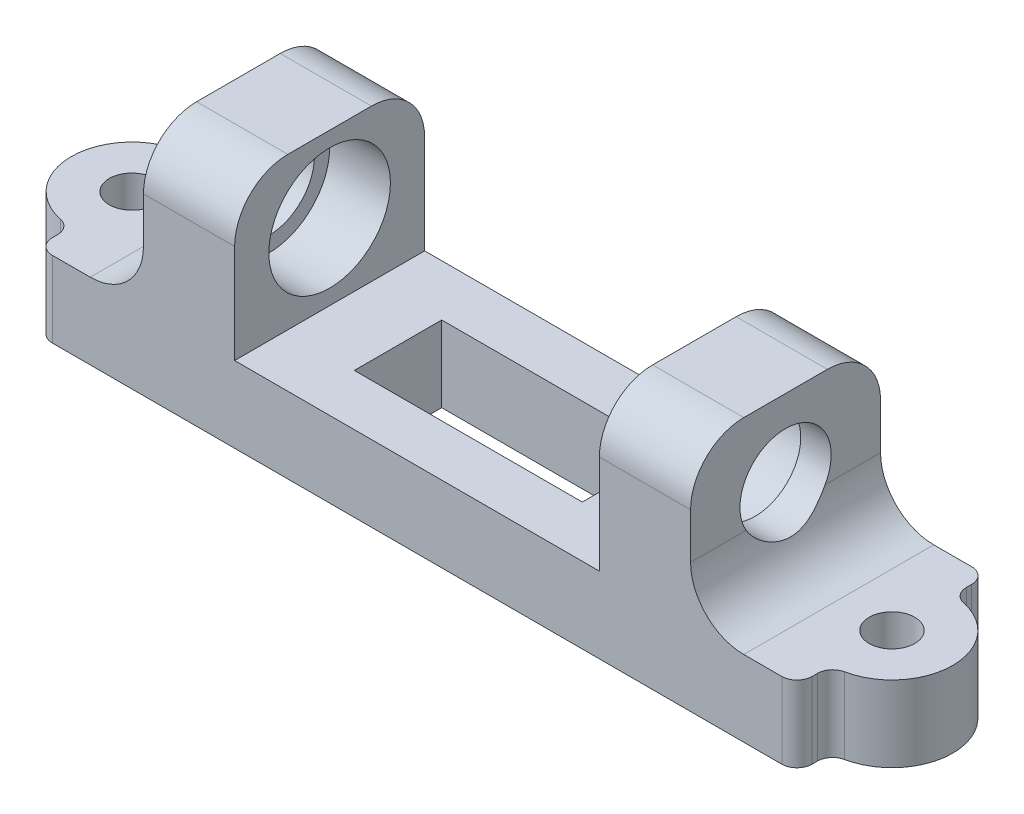
SolidWorks part; units mm, degrees
ref_plane "Front Plane" through (0, 0, 0) normal (0, 0, 1) x (1, 0, 0)
ref_plane "Top Plane" through (0, 0, 0) normal (0, 1, 0) x (1, 0, 0)
ref_plane "Right Plane" through (0, 0, 0) normal (1, 0, 0) x (0, 0, -1)
sketch "Sketch1" plane through (0, 0, 0) normal (0, 1, 0) x (1, 0, 0)
  line L0 (-25, -6.25) -> (-25, 6.25)
  line L1 (-25, -6.25) -> (25, -6.25)
  line L2 (-25, 6.25) -> (25, 6.25)
  line L3 (25, -6.25) -> (25, 6.25)
  line L4 (-25, -6.25) -> (25, 6.25) construction
  line L5 (-25, 6.25) -> (25, -6.25) construction
  circle A0 centre (-25, 0) radius 1.5
  circle A1 centre (25, 0) radius 1.5
  circle A2 centre (-25, 0) radius 4
  circle A3 centre (25, 0) radius 4
  point P1 (0, 0)
  dimension "D3" = 3
  dimension "D4" = 3
  dimension "D5" = 8
  dimension "D6" = 8
  dimension "D1" = 50
  dimension "D2" = 12.5
extrude "Boss-Extrude1" add sketch "Sketch1" along normal blind 5 contours A3 L3 L2 L0 A2 L1 | L0 A2 A0 | L0 A2 A0 | L3 A3 A1 | L3 A3 A1 region at (0, 0, 0) region at (-26.8713, 0, 0) region at (-23.1287, 0, 0) region at (23.1287, 0, 0) region at (26.8713, 0, 0)
sketch "Sketch2" plane through (0, 5, 0) normal (0, 1, 0) x (1, 0, 0)
  line L0 (-25, 1.5) -> (-25, -1.5)
  line L1 (-25, 0) -> (-15, 0)
  line L2 (-18, -6.25) -> (-18, 6.25)
  line L3 (-18, -6.25) -> (-12, -6.25)
  line L4 (-18, 6.25) -> (-12, 6.25)
  line L5 (-12, -6.25) -> (-12, 6.25)
  line L6 (-18, -6.25) -> (-12, 6.25) construction
  line L7 (-18, 6.25) -> (-12, -6.25) construction
  circle A0 centre (-25, 0) radius 1.5 construction
  dimension "D1" = 10
  dimension "D2" = 6
  dimension "D3" = 12.5
extrude "Boss-Extrude2" add sketch "Sketch2" along normal blind 10 contours L3 L5 L4 L2 region at (-17.8613, 5, 3.125)
sketch "Sketch3" plane through (-12, 0, 0) normal (1, 0, 0) x (0, 0, -1)
  line L0 (0, 15) -> (0, 5)
  line L1 (-6.25, 15) -> (6.25, 15) construction
  line L2 (-6.25, 5) -> (6.25, 5) construction
  circle A0 centre (0, 10) radius 4
  circle A1 centre (0, 10) radius 3
  dimension "D1" = 8
  dimension "D2" = 6
extrude "Cut-Extrude1" cut sketch "Sketch3" against normal blind 4 contours A0
extrude "Cut-Extrude2" cut sketch "Sketch3<3>" against normal through all contours A1
sketch "Sketch3<3>" plane through (-12, 0, 0) normal (1, 0, 0) x (0, 0, -1) same geometry as "Sketch3"
fillet "Fillet6" radius 3.5 1 edges at (-18, 5, 0) type face fillet first side face at (-18, 10, 3) second side face at (-25, 5, 1.5)
fillet "Fillet7" radius 3.5 1 edges at (-15, 15, -6.25) type face fillet first side face at (-8.975, 6.4195, -6.25) second side face at (-15, 15, 0)
fillet "Fillet8" radius 3.5 1 edges at (-15, 15, 6.25) type face fillet first side face at (-8.975, 6.4195, 6.25) second side face at (-15, 15, 1.75)
mirror "Mirror4" about plane through (0, 0, 0) normal (1, 0, 0) of "Cut-Extrude2", "Cut-Extrude1", "Boss-Extrude2"
fillet "Fillet9" radius 3.5 1 edges at (15, 15, -6.25) type face fillet first side face at (15, 15, 0) second side face at (-1.5981, 6.9827, -6.25)
fillet "Fillet10" radius 3.5 1 edges at (15, 15, 6.25) type face fillet first side face at (-1.5981, 6.9827, 6.25) second side face at (15, 15, 1.75)
fillet "Fillet11" radius 3.5 1 edges at (18, 5, 0) type face fillet first side face at (18, 10, 3) second side face at (25, 5, 1.5)
fillet "Fillet12" radius 1 1 edges at (25, 2.5, -6.25) type face fillet first side face at (25, 2.5, -5.125) second side face at (0, 6.5393, -6.25)
fillet "Fillet13" radius 1 1 edges at (25, 2.5, 6.25) type face fillet first side face at (25, 2.5, 5.125) second side face at (0, 6.5393, 6.25)
fillet "Fillet14" radius 1 1 edges at (-25, 2.5, 6.25) type face fillet first side face at (-0.1429, 6.5393, 6.25) second side face at (-25, 2.5, 5.125)
fillet "Fillet15" radius 1 1 edges at (-25, 2.5, -6.25) type face fillet first side face at (-25, 2.5, -5.125) second side face at (-0.1429, 6.5393, -6.25)
fillet "Fillet16" radius 1 1 edges at (-25, 2.5, -4) type face fillet first side face at (-25, 2.5, -4.625) second side face at (-27, 2.5, 0)
fillet "Fillet17" radius 1 1 edges at (-25, 2.5, 4) type face fillet first side face at (-27.1899, 2.5, 0.2212) second side face at (-25, 2.5, 4.625)
fillet "Fillet18" radius 1 1 edges at (25, 2.5, 4) type face fillet first side face at (27, 2.5, 0) second side face at (25, 2.5, 4.625)
fillet "Fillet19" radius 1 1 edges at (25, 2.5, -4) type face fillet first side face at (25, 2.5, -4.625) second side face at (27.1899, 2.5, -0.2212)
sketch "Sketch4" plane through (0, 5, 0) normal (0, 1, 0) x (1, 0, 0)
  line L0 (-7.5, -2.875) -> (7.5, -2.875)
  line L1 (-7.5, -2.875) -> (-7.5, 2.875)
  line L2 (7.5, -2.875) -> (7.5, 2.875)
  line L3 (-7.5, 2.875) -> (7.5, 2.875)
  line L4 (-7.5, -2.875) -> (7.5, 2.875) construction
  line L5 (7.5, -2.875) -> (-7.5, 2.875) construction
  point P1 (0, 0)
  dimension "D1" = 15
  dimension "D2" = 5.75
extrude "Cut-Extrude3" cut sketch "Sketch4" against normal through all contours L0 L1 L3 L2
